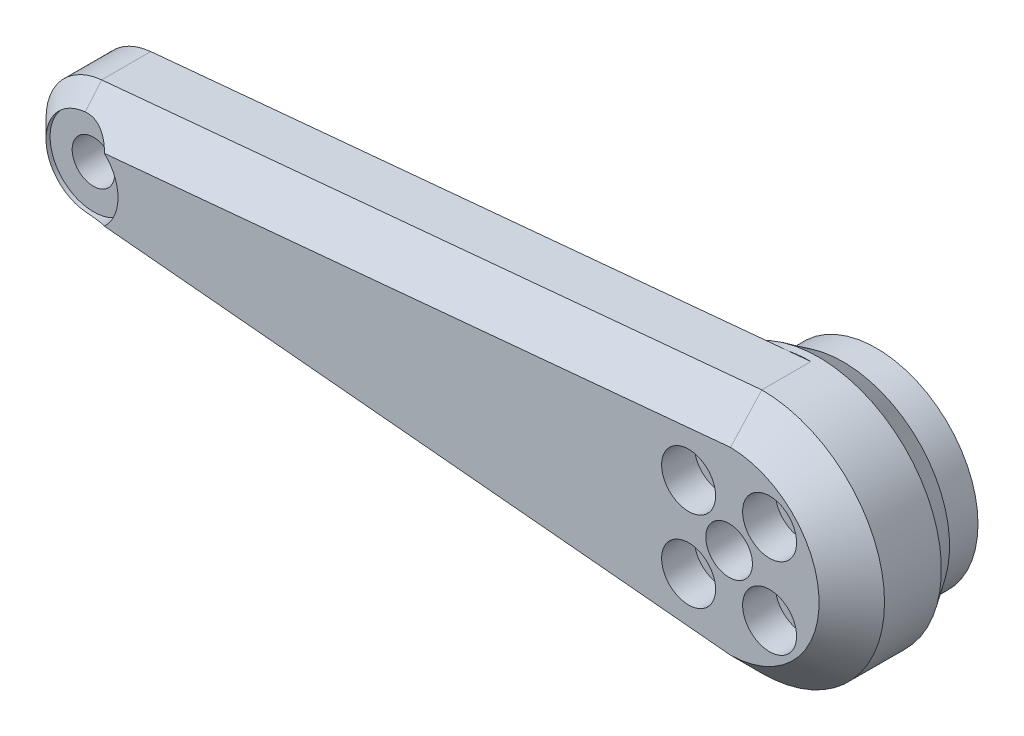
SolidWorks part; units mm, degrees
material "ABS"
ref_plane "Front Plane" through (0, 0, 0) normal (0, 0, 1) x (1, 0, 0)
ref_plane "Top Plane" through (0, 0, 0) normal (0, 1, 0) x (1, 0, 0)
ref_plane "Right Plane" through (0, 0, 0) normal (1, 0, 0) x (0, 0, -1)
sketch "Sketch1" plane through (0, 0, 0) normal (0, 0, 1) x (1, 0, 0)
  line L0 (0, 0) -> (-312.3779, 0) construction
  line L1 (-80.697, 7.4675) -> (0, 15)
  line L2 (-80.697, -7.4675) -> (0, -15)
  circle A0 centre (0, 0) radius 15
  circle A1 centre (-80, 0) radius 7.5
  dimension "D1" = 30
  dimension "D2" = 15
  dimension "D3" = 80
extrude "Boss-Extrude1" add sketch "Sketch1" along normal blind 10 contours L0 A0 L1 A1 | A0 L0 A1 L2 | A1 L0 | L0 A1 | L1 A0 L2 region at (-40.485, -5.8766, 0) region at (-40.485, 5.8766, 0) region at (0.0005, 0, 0) region at (-80, -3.1831, 0) region at (-80, 3.1831, 0)
sketch "Sketch3" plane through (0, 0, 0) normal (0, 0, -1) x (-1, 0, 0)
  circle A0 centre (0, 0) radius 12.425
  dimension "D1" = 24.85
chamfer "Chamfer1" distance 4 angle 45 4 edges at (-40.3485, -11.2338, 10) (-87.5, 0, 10) (15, 0, 10) (-40.3485, 11.2338, 10)
sketch "Sketch6" plane through (0, 0, 10) normal (0, 0, 1) x (1, 0, 0)
  circle A2 centre (-80, 0) radius 2
  dimension "D1" = 4
extrude "Cut-Extrude4" cut sketch "Sketch6" against normal blind 5 contours A2
sketch "Sketch7" plane through (0, 0, 0) normal (0, 0, -1) x (-1, 0, 0)
  arc A0 (80.697, -7.4675) -> (80.697, 7.4675) centre (80, 0) ccw construction
  arc A1 (80.697, -7.4675) -> (80.697, 7.4675) centre (80, 0) ccw
  circle A2 centre (80, 0) radius 2.1
  dimension "D1" = 4.2
extrude "Cut-Extrude5" cut sketch "Sketch7" against normal blind 5 contours A2 region at (-80, 0, 0)
sketch "Sketch8" plane through (0, 0, 10) normal (0, 0, 1) x (1, 0, 0)
  circle A1 centre (-80, 0) radius 2
  circle A2 centre (-80, 0) radius 2.1
  dimension "D1" = 4.2
extrude "Cut-Extrude6" cut sketch "Sketch8" against normal through all contours A2 region at (-82.0406, 0, 10)
extrude "Boss-Extrude3" add sketch "Sketch3" along normal blind 8
sketch "Sketch9" plane through (0, 0, -8) normal (0, 0, -1) x (-1, 0, 0)
  line L0 (-4.9497, -4.9497) -> (4.9497, 4.9497) construction
  line L1 (-4.9497, 4.9497) -> (4.9497, -4.9497) construction
  circle A1 centre (4.9497, 4.9497) radius 1.75
  circle A2 centre (-4.9497, 4.9497) radius 1.75
  circle A3 centre (-4.9497, -4.9497) radius 1.75
  circle A4 centre (4.9497, -4.9497) radius 1.75
  point P5 (0, 0)
  point P10 (0, 0)
  dimension "D1" = 90
  dimension "D5" = 3.5
  dimension "D6" = 14
extrude "Cut-Extrude7" cut sketch "Sketch9" against normal through all
sketch "Sketch10" plane through (0, 0, 10) normal (0, 0, 1) x (1, 0, 0)
  circle A0 centre (0, 0) radius 2.85
  dimension "D1" = 5.7
extrude "Cut-Extrude8" cut sketch "Sketch10" against normal through all
sketch "Sketch11" plane through (0, 0, 0) normal (0, 0, -1) x (-1, 0, 0)
  circle A0 centre (0, 0) radius 12.425 construction
  circle A1 centre (0, 0) radius 12.425
  circle A2 centre (0, 0) radius 15
  dimension "D1" = 30
extrude "Boss-Extrude4" add sketch "Sketch11" along normal blind 3.95
sketch "Sketch12" plane through (0, 0, 10) normal (0, 0, 1) x (1, 0, 0)
  circle A0 centre (-80, 0) radius 2.6
  dimension "D1" = 5.2
extrude "Cut-Extrude10" cut sketch "Sketch12" against normal through all and the other way through all
sketch "Sketch13" plane through (0, 0, 0) normal (0, 0, -1) x (-1, 0, 0)
  circle A0 centre (80, 0) radius 5.2
  dimension "D1" = 10.4
extrude "Cut-Extrude11" cut sketch "Sketch13" against normal blind 2.3
sketch "Sketch14" plane through (0, 0, 10) normal (0, 0, 1) x (1, 0, 0)
  circle A0 centre (-80, 0) radius 5.3
  dimension "D1" = 10.6
extrude "Cut-Extrude12" cut sketch "Sketch14" against normal blind 2.3
chamfer "Chamfer2" distance 3 distance2 2 1 edges at (-15, 0, -3.95) first distance on face at (-0.4647, 0, 2)
sketch "Sketch15" plane through (0, 0, 10) normal (0, 0, 1) x (1, 0, 0)
  circle A0 centre (4.9497, 4.9497) radius 3.3
  circle A1 centre (4.9497, -4.9497) radius 3.3
  circle A2 centre (-4.9497, -4.9497) radius 3.3
  circle A3 centre (-4.9497, 4.9497) radius 3.3
  circle A4 centre (4.9497, -4.9497) radius 1.75 construction
  dimension "D1" = 6.6
extrude "Cut-Extrude13" cut sketch "Sketch15" against normal blind 4
